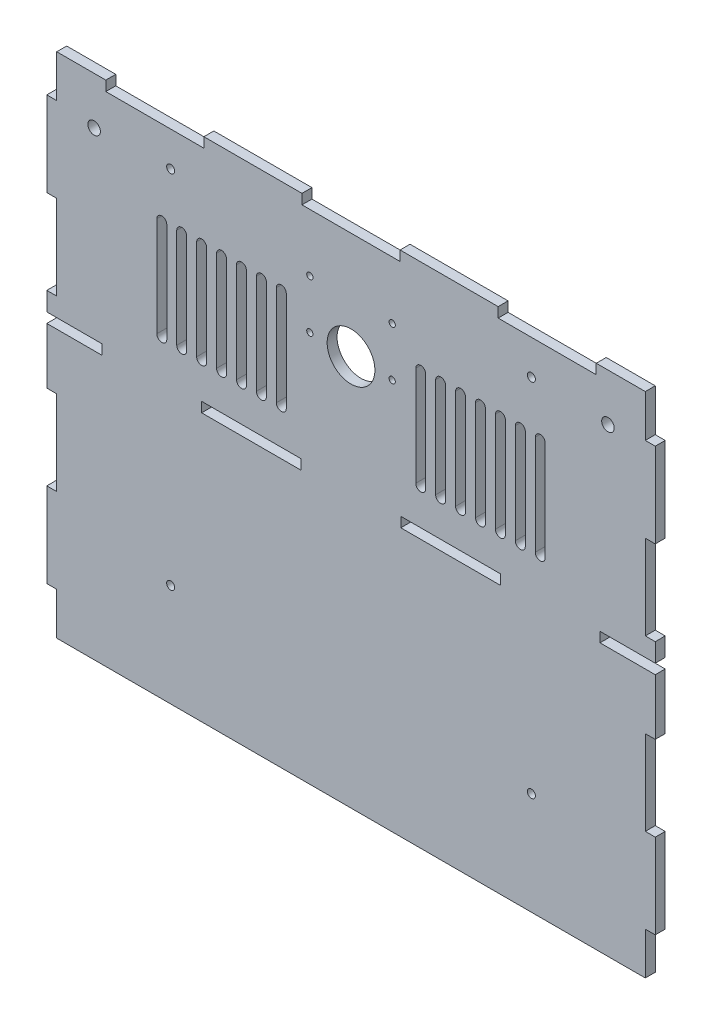
SolidWorks part; units mm, degrees
ref_plane "Front Plane" through (0, 0, 0) normal (0, 0, 1) x (1, 0, 0)
ref_plane "Top Plane" through (0, 0, 0) normal (0, 1, 0) x (1, 0, 0)
ref_plane "Right Plane" through (0, 0, 0) normal (1, 0, 0) x (0, 0, -1)
sketch "Sketch1" plane through (0, 0, 0) normal (0, 0, 1) x (1, 0, 0)
  line L1 (-75.057, 64.77) -> (75.057, 64.77)
  line L2 (-75.057, 64.77) -> (-75.057, -64.77)
  line L3 (-75.057, -64.77) -> (75.057, -64.77)
  line L4 (75.057, 64.77) -> (75.057, -64.77)
  line L5 (0, -64.77) -> (0, 64.77) construction
  line L6 (-75.057, 0) -> (75.057, 0) construction
  point P0 (0, 0)
  dimension "D1" = 150.114
  dimension "D2" = 129.54
extrude "Boss-Extrude1" add sketch "Sketch1" along normal blind 2.54
sketch "Sketch4" plane through (0, 0, 2.54) normal (0, 0, 1) x (1, 0, 0)
  line L0 (75.057, 64.77) -> (-75.057, 64.77) construction
  line L1 (-62.5475, 64.77) -> (-37.5285, 64.77)
  line L2 (-62.5475, 64.77) -> (-62.5475, 62.23)
  line L3 (-62.5475, 62.23) -> (-37.5285, 62.23)
  line L4 (-37.5285, 64.77) -> (-37.5285, 62.23)
  line L5 (-75.057, 64.77) -> (-75.057, -64.77) construction
  dimension "D1" = 2.54
  dimension "D2" = 25.019
  dimension "D3" = 12.5095
extrude "Cut-Extrude1" cut sketch "Sketch4" against normal through all
pattern_linear "LPattern1" count 3 spacing 50.038 along (1, 0, 0) of "Cut-Extrude1"
sketch "Sketch5" plane through (0, 0, 2.54) normal (0, 0, 1) x (1, 0, 0)
  line L0 (-75.057, 64.77) -> (-75.057, -64.77) construction
  line L1 (-75.057, 53.975) -> (-77.597, 53.975)
  line L2 (-75.057, 53.975) -> (-75.057, 32.385)
  line L3 (-75.057, 32.385) -> (-77.597, 32.385)
  line L4 (-77.597, 53.975) -> (-77.597, 32.385)
  line L5 (-62.5475, 64.77) -> (-75.057, 64.77) construction
  dimension "D1" = 2.54
  dimension "D2" = 21.59
  dimension "D3" = 10.795
extrude "Boss-Extrude3" add sketch "Sketch5" against normal blind 2.54
pattern_linear "LPattern2" count 3 spacing 43.18 along (0, -1, 0) count 2 spacing 152.654 along (1, 0, 0) of "Boss-Extrude3"
hole_wizard "Tap Drill for M2.5x0.45 Tap1" positions "Sketch6" profile "Sketch7" hole size "M2.5x0.45" standard "ANSI Metric" end condition through all
sketch "Sketch6" plane through (0, 0, 2.54) normal (0, 0, 1) x (1, 0, 0)
  line L2 (75.057, 64.77) -> (62.5475, 64.77) construction
  line L4 (77.597, 32.385) -> (77.597, 53.975) construction
  point P0 (46, 53.4135)
  point P2 (-46, 53.4135)
  point P4 (-46, -38.5865)
  point P6 (46, -38.5865)
  dimension "D1" = 92
  dimension "D2" = 92
  dimension "D4" = 11.3565
  dimension "D7" = 31.597
sketch "Sketch7" plane through (46, 53.4135, 2.54) normal (1, 0, 0) x (0, -1, 0)
  line L0 (0, 0) -> (0, 2.54)
  line L1 (0, 2.54) -> (1.025, 2.54)
  line L2 (1.025, 2.54) -> (1.025, 0)
  line L5 (1.025, 0) -> (0, 0)
  line L11 (0, -6.35) -> (0, 107.95) construction
  dimension "Thru Hole Dia." = 2.05
  dimension "Thru Hole Depth" = 2.54
hole_wizard "M3 Clearance Hole1" positions "Sketch8" profile "Sketch9" hole size "M3" standard "ANSI Metric"
sketch "Sketch8" plane through (0, 0, 2.54) normal (0, 0, 1) x (1, 0, 0)
  line L0 (-75.057, 64.77) -> (-75.057, 53.975) construction
  line L1 (-62.5475, 62.23) -> (-37.5285, 62.23) construction
  line L2 (37.5285, 62.23) -> (62.5475, 62.23) construction
  line L3 (75.057, 53.975) -> (75.057, 64.77) construction
  point P0 (-65.532, 52.705)
  point P2 (65.532, 52.705)
  dimension "D1" = 9.525
  dimension "D2" = 9.525
  dimension "D3" = 9.525
  dimension "D4" = 9.525
sketch "Sketch9" plane through (-65.532, 52.705, 2.54) normal (1, 0, 0) x (0, -1, 0)
  line L0 (0, 0) -> (0, 10.3594)
  line L1 (0, 10.3594) -> (1.6, 9.398)
  line L2 (1.6, 9.398) -> (1.6, 0)
  line L5 (1.6, 0) -> (0, 0)
  line L10 (0, 10.3594) -> (-1.6, 9.398) construction
  line L11 (0, -6.35) -> (0, 107.95) construction
  dimension "Hole Dia." = 3.2
  dimension "Hole Depth" = 9.398
  dimension "Drill Angle" = 118
sketch "Sketch10" plane through (0, 0, 0) normal (0, 0, -1) x (-1, 0, 0)
  circle A0 centre (0, 34.98) radius 6.096
  point P2 (0, 0)
  dimension "D1" = 12.192
  dimension "D2" = 34.98
extrude "Cut-Extrude2" cut sketch "Sketch10" against normal through all
hole_wizard "Tap Drill for M2x0.4 Tap1" positions "Sketch11" profile "Sketch12" hole size "M2x0.4" standard "ANSI Metric" end condition through all
sketch "Sketch11" plane through (0, 0, 0) normal (0, 0, -1) x (-1, 0, 0)
  point P0 (-10.5, 47.53)
  point P2 (-10.5, 35.03)
  point P4 (10.5, 47.53)
  point P6 (10.5, 35.03)
  point P8 (11.191, 34.3071)
  point P9 (10.5, 35.03)
  point P11 (0, 0)
  point P12 (0, 0)
  point P13 (0, 0)
  point P14 (0, 0)
  dimension "D1" = 12.5
  dimension "D2" = 35.03
  dimension "D3" = 21
  dimension "D4" = 10.5
sketch "Sketch12" plane through (10.5, 47.53, 0) normal (1, 0, 0) x (0, 1, 0)
  line L0 (0, 0) -> (0, 2.54)
  line L1 (0, 2.54) -> (0.8, 2.54)
  line L2 (0.8, 2.54) -> (0.8, 0)
  line L5 (0.8, 0) -> (0, 0)
  line L11 (0, -6.35) -> (0, 107.95) construction
  dimension "Thru Hole Dia." = 1.6
  dimension "Thru Hole Depth" = 2.54
sketch "Sketch13" plane through (0, 0, 2.54) normal (0, 0, 1) x (1, 0, 0)
  line L0 (-75.057, -10.795) -> (-75.057, -32.385) construction
  line L1 (-38.1, 6.0325) -> (-12.7, 6.0325)
  line L2 (-38.1, 6.0325) -> (-38.1, 3.4925)
  line L3 (-38.1, 3.4925) -> (-12.7, 3.4925)
  line L4 (-12.7, 6.0325) -> (-12.7, 3.4925)
  line L5 (-75.057, -64.77) -> (75.057, -64.77) construction
  line L7 (-88.9, 6.0325) -> (-63.5, 6.0325)
  line L8 (-88.9, 6.0325) -> (-88.9, 3.4925)
  line L9 (-88.9, 3.4925) -> (-63.5, 3.4925)
  line L10 (-63.5, 6.0325) -> (-63.5, 3.4925)
  dimension "D1" = 2.54
  dimension "D2" = 36.957
  dimension "D3" = 25.4
  dimension "D4" = 68.2625
  dimension "D5" = 25.4
  dimension "D6" = 25.4
extrude "Cut-Extrude3" cut sketch "Sketch13" against normal through all
mirror "Mirror1" about plane through (0, 0, 0) normal (1, 0, 0) of "Cut-Extrude3"
sketch "Sketch14" plane through (0, 0, 2.54) normal (0, 0, 1) x (1, 0, 0)
  line L0 (-17.78, 40.64) -> (-17.78, 15.24) construction
  line L1 (-16.51, 40.64) -> (-16.51, 15.24)
  line L2 (-19.05, 40.64) -> (-19.05, 15.24)
  arc A0 (-16.51, 40.64) -> (-19.05, 40.64) centre (-17.78, 40.64) ccw
  arc A1 (-19.05, 15.24) -> (-16.51, 15.24) centre (-17.78, 15.24) ccw
  point P2 (-17.78, 27.94)
  point P7 (-33.2437, 32.1524)
  point P8 (-15.7514, 28.2879)
  dimension "D1" = 2.54
  dimension "D2" = 25.4
  dimension "D3" = 17.78
  dimension "D4" = 27.94
extrude "Cut-Extrude4" cut sketch "Sketch14" against normal through all
pattern_linear "LPattern3" count 7 spacing 5.08 along (-1, 0, 0) count 14 spacing 5.08 along (1, 0, 0) of "Cut-Extrude4"
